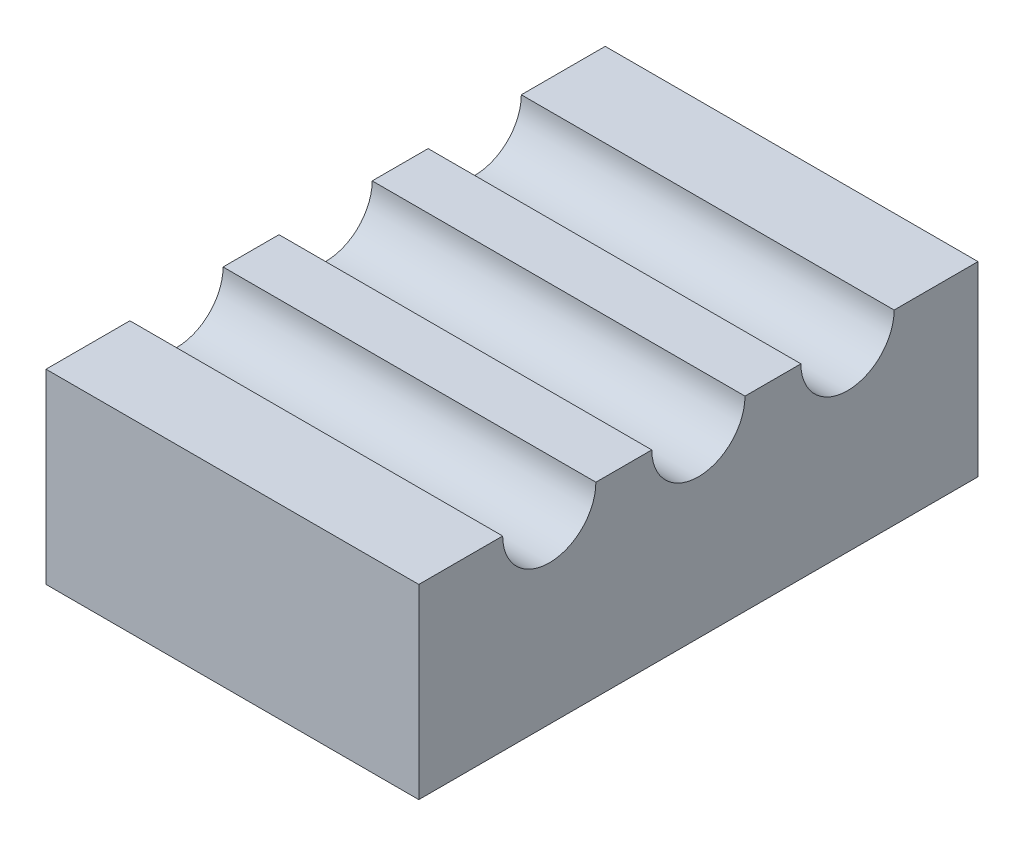
SolidWorks part; units mm, degrees
material "ABS PC"
ref_plane "Front Plane" through (0, 0, 0) normal (0, 0, 1) x (1, 0, 0)
ref_plane "Top Plane" through (0, 0, 0) normal (0, 1, 0) x (1, 0, 0)
ref_plane "Right Plane" through (0, 0, 0) normal (1, 0, 0) x (0, 0, -1)
sketch "Sketch1" plane through (0, 0, 0) normal (0, 1, 0) x (1, 0, 0)
  line L1 (-5, -7.5) -> (5, -7.5)
  line L2 (-5, -7.5) -> (-5, 7.5)
  line L3 (-5, 7.5) -> (5, 7.5)
  line L4 (5, -7.5) -> (5, 7.5)
  line L5 (-5, -7.5) -> (5, 7.5) construction
  line L6 (-5, 7.5) -> (5, -7.5) construction
  point P0 (0, 0)
  dimension "D1" = 10
  dimension "D2" = 15
extrude "Boss-Extrude1" add sketch "Sketch1" along normal blind 5
sketch "Sketch2" plane through (5, 0, 0) normal (1, 0, 0) x (0, 0, -1)
  line L0 (0, 5.6176) -> (0, -0.8561) construction
  line L1 (-4, 5) -> (0, 5) construction
  line L3 (-7.5, 5) -> (7.5, 5) construction
  circle A0 centre (0, 5) radius 1.25
  circle A1 centre (-4, 5) radius 1.25
  circle A2 centre (4, 5) radius 1.25
  point P9 (-4, 5)
  dimension "D1" = 2.5
  dimension "D3" = 4
extrude "Cut-Extrude1" cut sketch "Sketch2" against normal through all
